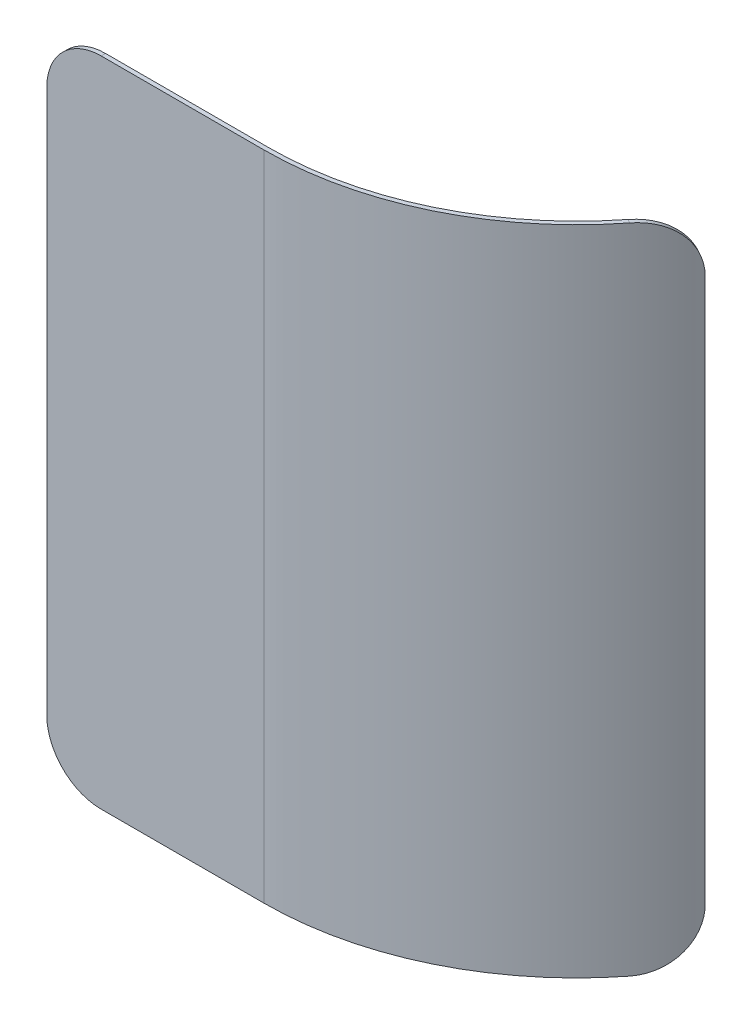
SolidWorks part; units mm, degrees
ref_plane "Front Plane" through (0, 0, 0) normal (0, 0, 1) x (1, 0, 0)
ref_plane "Top Plane" through (0, 0, 0) normal (0, 1, 0) x (1, 0, 0)
ref_plane "Right Plane" through (0, 0, 0) normal (1, 0, 0) x (0, 0, -1)
sketch "Sketch1" plane through (0, 0, 0) normal (0, 1, 0) x (1, 0, 0)
  line L0 (0, 0) -> (50.8, 0)
  line L1 (-55, 0) -> (55, 0) construction
  arc A0 (50.8, 0) -> (114.2949, 38.1) centre (50.8, 71.9582) ccw
  dimension "D1" = 71.9582
  dimension "D2" = 50.8
  dimension "D3" = 38.1
extrude "Extrude-Thin1" add sketch "Sketch1" along normal blind 152.4 thin thin type one direction wall 1.016
fillet "Fillet1" radius 12.7 4 edges at (0, 0, 0.508) (0, 152.4, 0.508) (114.7432, 0, -37.861) (114.7432, 152.4, -37.861)
